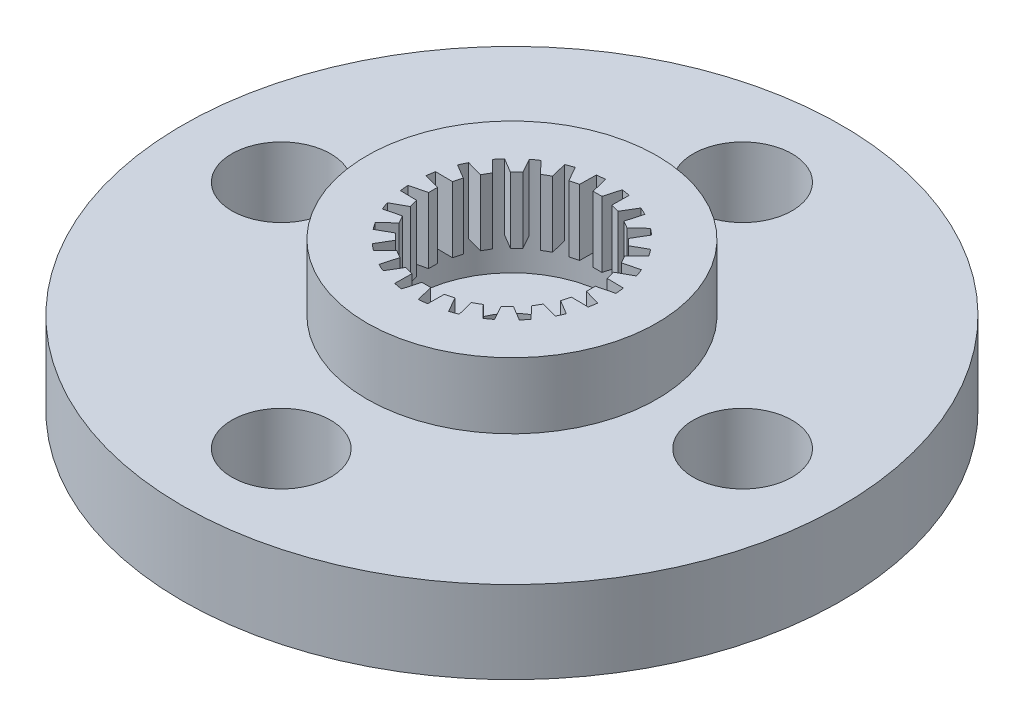
SolidWorks part; units mm, degrees
note: '?' marks a value the reader was unsure of.
ref_plane "前视基准面" through (0, 0, 0) normal (0, 0, 1) x (1, 0, 0)
ref_plane "上视基准面" through (0, 0, 0) normal (0, 1, 0) x (1, 0, 0)
ref_plane "右视基准面" through (0, 0, 0) normal (1, 0, 0) x (0, 0, -1)
sketch "草图4" plane through (0, 0, 0) normal (0, 1, 0) x (1, 0, 0)
  circle A0 centre (0, 0) radius 10
  dimension "D1" = 20
extrude "凸台-拉伸2" add sketch "草图4" along normal blind 2.5
ref_plane "基准面7" through (0, 2.5, 0) normal (0, 1, 0) x (1, 0, 0)
sketch "草图6" plane through (0, 2.5, 0) normal (0, 1, 0) x (1, 0, 0)
  circle A0 centre (0, 0) radius 7 construction
  circle A1 centre (0, 7) radius 1.5
  circle A2 centre (0, 0) radius 1.5
  circle A3 centre (7, 0) radius 1.5
  circle A4 centre (-7, 0) radius 1.5
  circle A5 centre (0, -7) radius 1.5
  dimension "D1" = 3
  dimension "D2" = 3
  dimension "D3" = 3
  dimension "D4" = 3
  dimension "D5" = 3
  dimension "D6" = 14
extrude "切除-拉伸9" cut sketch "草图6" against normal blind 2.5
sketch "草图7" plane through (0, 2.5, 0) normal (0, 1, 0) x (1, 0, 0)
  circle A0 centre (0, 0) radius 4.4
  dimension "D1" = 8.8
extrude "凸台-拉伸3" add sketch "草图7" along normal blind 2
ref_plane "基准面8" through (0, 4.5, 0) normal (0, 1, 0) x (1, 0, 0)
sketch "草图8" plane through (0, 4.5, 0) normal (0, 1, 0) x (1, 0, 0)
  circle A0 centre (0, 0) radius 3
  dimension "D1" = 6
extrude "切除-拉伸10" cut sketch "草图8" against normal blind 3
ref_axis "基准轴1" through (0, 1.5, 0) along (0, 1, 0)?
sketch "草图14" plane through (0, 4.5, 0) normal (0, 1, 0) x (1, 0, 0)
  line L0 (2.9769, -0.3715) -> (2.4958, -0.2354)
  line L1 (2.4958, -0.2354) -> (2.4958, 0.0323)
  line L2 (2.4958, 0.0323) -> (2.9958, 0.1588)
  arc A0 (2.9769, -0.3715) -> (2.9958, 0.1588) centre (0, 0) ccw
  dimension "D3" = 3
  dimension "D1" = 30
  dimension "D2" = 0.5
  dimension "0.5" = 0.5
extrude "凸台-拉伸5" add sketch "草图14" against normal blind 2
pattern_circular "阵列(圆周)1" count 24 over 360 about axis through (0, 0, 0) along (0, 1, 0) of "凸台-拉伸5"
